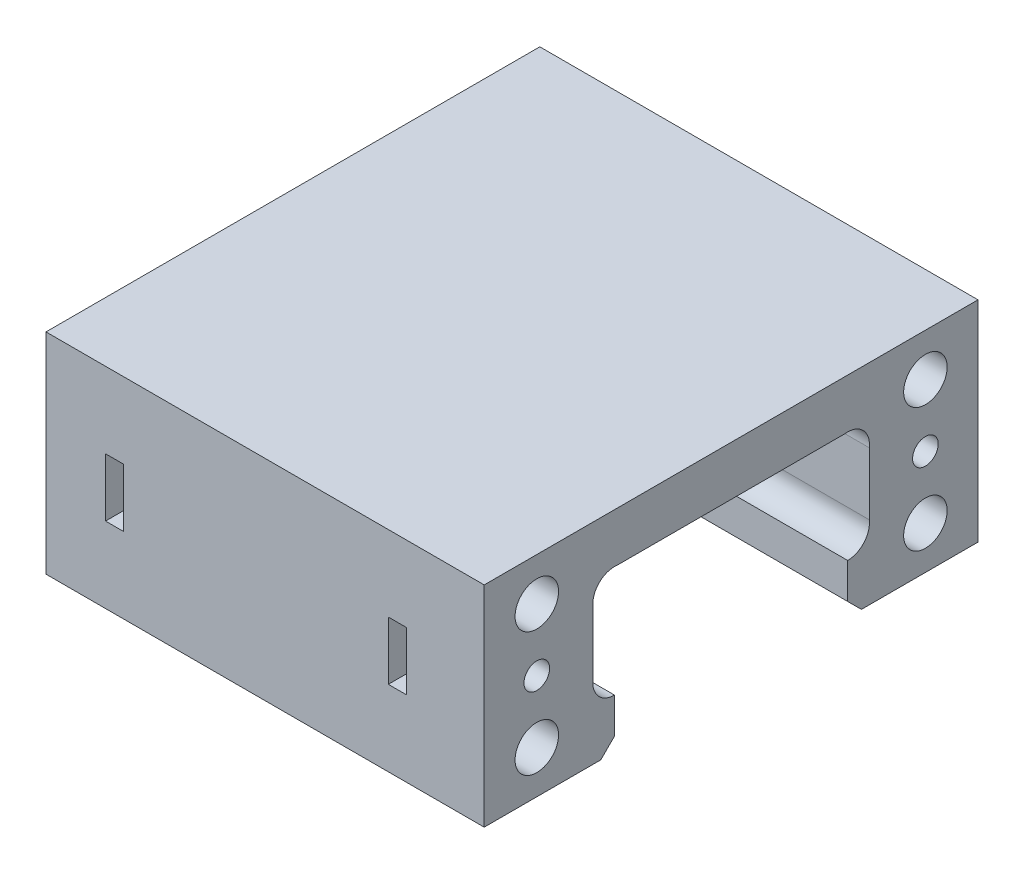
SolidWorks part; units mm, degrees
ref_plane "Front Plane" through (0, 0, 0) normal (0, 0, 1) x (1, 0, 0)
ref_plane "Top Plane" through (0, 0, 0) normal (0, 1, 0) x (1, 0, 0)
ref_plane "Right Plane" through (0, 0, 0) normal (1, 0, 0) x (0, 0, -1)
sketch "Sketch1" plane through (0, 0, 0) normal (1, 0, 0) x (0, 0, -1)
  line L0 (0, 0) -> (30, 0)
  line L1 (0, 0) -> (0, 5)
  line L2 (0, 5) -> (2.7781, 7.7781)
  line L3 (2.7781, 7.7781) -> (2.7781, 14.2781)
  line L4 (2.7781, 14.2781) -> (0, 14.2781) construction
  line L5 (0, 14.2781) -> (0, 23) construction
  line L6 (0, 23) -> (30, 23) construction
  line L12 (15, 0) -> (15, 23) construction
  line L13 (27.2219, 23) -> (2.7781, 23)
  line L14 (0, 20.2219) -> (0, 17.0562)
  line L15 (30, 14.2781) -> (30, 23) construction
  line L16 (27.2219, 14.2781) -> (30, 14.2781) construction
  line L17 (30, 20.2219) -> (30, 17.0562)
  line L18 (27.2219, 7.7781) -> (27.2219, 14.2781)
  line L19 (30, 5) -> (27.2219, 7.7781)
  line L20 (30, 0) -> (30, 5)
  arc A0 (2.7781, 14.2781) -> (0, 17.0562) centre (0, 14.2781) ccw
  arc A1 (0, 20.2219) -> (2.7781, 23) centre (0, 23) ccw
  arc A2 (30, 20.2219) -> (27.2219, 23) centre (30, 23) cw
  arc A3 (27.2219, 14.2781) -> (30, 17.0562) centre (30, 14.2781) cw
  dimension "D1" = 5.5563
  dimension "D2" = 15
  dimension "D3" = 23
  dimension "D4" = 45
  dimension "D5" = 6.5
  dimension "D6" = 5
sketch "Sketch2" plane through (0, 0, 0) normal (1, 0, 0) x (0, 0, -1)
  line L0 (-10, 26.6391) -> (-10, 32.1391) construction
  line L1 (15, 23) -> (15, -0.4684) construction
  line L2 (-10, 10.6391) -> (-10, 5.1391) construction
  line L3 (0, 25.7781) -> (30, 25.7781)
  line L4 (0, 11.5) -> (0, 6.9068)
  line L5 (0, 6.9068) -> (-1.7678, 5.1391)
  line L6 (-1.7678, 5.1391) -> (-16.7678, 5.1391)
  line L7 (-16.7678, 5.1391) -> (-16.7678, 32.1391)
  line L8 (-10, 26.6391) -> (0, 23) construction
  line L9 (0, 23) -> (0, 14.2781) construction
  line L10 (0, 14.2781) -> (-10, 10.6391) construction
  line L11 (-10, 10.6391) -> (-10, 26.6391) construction
  line L12 (0, 18.6391) -> (-10, 18.6391) construction
  line L13 (-16.7678, 32.1391) -> (46.7678, 32.1391)
  line L14 (15, 32.1391) -> (15, 25.7781) construction
  line L15 (-2.7781, 14.2781) -> (-2.7781, 23)
  line L16 (0, 5) -> (2.7781, 7.7781) construction
  line L17 (15, 0) -> (15, 23) construction
  line L18 (30, 18.6391) -> (40, 18.6391) construction
  line L19 (40, 10.6391) -> (40, 26.6391) construction
  line L20 (30, 14.2781) -> (40, 10.6391) construction
  line L21 (30, 23) -> (30, 14.2781) construction
  line L22 (40, 26.6391) -> (30, 23) construction
  line L23 (40, 10.6391) -> (40, 5.1391) construction
  line L24 (40, 26.6391) -> (40, 32.1391) construction
  line L25 (32.7781, 14.2781) -> (32.7781, 23)
  line L26 (46.7678, 5.1391) -> (46.7678, 32.1391)
  line L27 (31.7678, 5.1391) -> (46.7678, 5.1391)
  line L28 (30, 6.9068) -> (31.7678, 5.1391)
  line L29 (30, 11.5) -> (30, 6.9068)
  arc A0 (0, 25.7781) -> (-2.7781, 23) centre (0, 23) ccw
  arc A1 (-2.7781, 14.2781) -> (0, 11.5) centre (0, 14.2781) ccw
  arc A2 (2.7781, 14.2781) -> (0, 17.0562) centre (0, 14.2781) ccw construction
  circle A3 centre (-10, 26.6391) radius 2.7781
  circle A4 centre (-10, 10.6391) radius 2.7781
  circle A5 centre (40, 10.6391) radius 2.7781
  circle A6 centre (40, 26.6391) radius 2.7781
  arc A7 (32.7781, 14.2781) -> (30, 11.5) centre (30, 14.2781) cw
  arc A8 (30, 25.7781) -> (32.7781, 23) centre (30, 23) cw
  dimension "D1" = 10
  dimension "D2" = 16
  dimension "D3" = 15
  dimension "D4" = 27
  dimension "D5" = 2.5
extrude "Boss-Extrude2" add sketch "Sketch2" along normal blind 56.3836
sketch "Sketch3" plane through (56.3836, 0, 0) normal (1, 0, 0) x (0, 0, -1)
  line L0 (-10, 26.6391) -> (-10, 10.6391) construction
  line L1 (15, 20.921) -> (15, 13.7492) construction
  line L2 (15, 200023) -> (15, -200000.4684) construction
  line L3 (-10, 18.6391) -> (15, 18.6391) construction
  circle A0 centre (-10, 18.6391) radius 1.651
  circle A1 centre (40, 18.6391) radius 1.651
  dimension "D1" = 3.302
extrude "Cut-Extrude1" cut sketch "Sketch3" against normal blind 22.1668
ref_plane "Plane1" through (14.3012, 0, 0) normal (1, 0, 0) x (0, 0, -1)
ref_plane "Plane2" through (0, 18.6391, 0) normal (0, -1, 0) x (0, 0, -1)
ref_axis "Axis1" through (-60.3203, 18.6391, 10) along (1, 0, 0)
ref_axis "Axis2" through (56.3836, 18.6391, -40) along (1, 0, 0)
sketch "Sketch4" plane through (0, 18.6391, 0) normal (0, -1, 0) x (0, 0, -1)
  line L0 (-16.7678, 56.3836) -> (-16.7678, 0) construction
  line L1 (-16.7678, 46.3836) -> (-6, 46.3836)
  line L2 (-16.7678, 46.3836) -> (-16.7678, 44.0436)
  line L3 (-16.7678, 44.0436) -> (-6, 44.0436)
  line L4 (-6, 46.3836) -> (-6, 44.0436)
  line L5 (46.7678, 56.3836) -> (46.7678, 0) construction
  line L6 (46.7678, 46.3836) -> (36, 46.3836)
  line L7 (46.7678, 46.3836) -> (46.7678, 44.0436)
  line L8 (46.7678, 44.0436) -> (36, 44.0436)
  line L9 (36, 46.3836) -> (36, 44.0436)
  line L10 (-16.7678, 56.3836) -> (-1.7678, 56.3836) construction
  line L11 (-16.7678, 7.66) -> (-6, 7.66)
  line L12 (-16.7678, 7.66) -> (-16.7678, 10)
  line L13 (-16.7678, 10) -> (-6, 10)
  line L14 (-6, 7.66) -> (-6, 10)
  line L15 (36, 7.66) -> (46.7678, 7.66)
  line L16 (36, 7.66) -> (36, 10)
  line L17 (36, 10) -> (46.7678, 10)
  line L18 (46.7678, 7.66) -> (46.7678, 10)
  line L19 (-16.7678, 0) -> (-1.7678, 0) construction
  line L20 (-10, -60.3203) -> (-10, 103.1706) construction
  dimension "D1" = 10
  dimension "D2" = 10
  dimension "D3" = 4
  dimension "D4" = 2.34
extrude "Cut-Extrude2" cut sketch "Sketch4" against normal mid plane 7.5
sketch "Sketch5" plane through (56.3836, 0, 0) normal (1, 0, 0) x (0, 0, -1)
  circle A0 centre (-10, 26.6391) radius 2.8
  circle A1 centre (0, 23) radius 2.8
  circle A2 centre (-10, 10.6391) radius 2.8
  circle A3 centre (40, 26.6391) radius 2.8
  circle A4 centre (40, 10.6391) radius 2.8
  circle A5 centre (30, 23) radius 2.8
  circle A6 centre (0, 14.2781) radius 2.8
  circle A7 centre (30, 14.2781) radius 2.8
  arc A8 (0, 25.7781) -> (-2.7781, 23) centre (0, 23) ccw construction
  arc A9 (-2.7781, 14.2781) -> (0, 11.5) centre (0, 14.2781) ccw construction
  arc A10 (30, 11.5) -> (32.7781, 14.2781) centre (30, 14.2781) ccw construction
  arc A11 (32.7781, 23) -> (30, 25.7781) centre (30, 23) ccw construction
  dimension "D1" = 5.6
extrude "Cut-Extrude3" cut sketch "Sketch5" against normal through all
ref_plane "Plane3" through (28.1918, 0, 0) normal (-1, 0, 0) x (0, 0, 1)
mirror "Mirror1" about plane through (28.1918, 0, 0) normal (-1, 0, 0) of "Cut-Extrude1"
